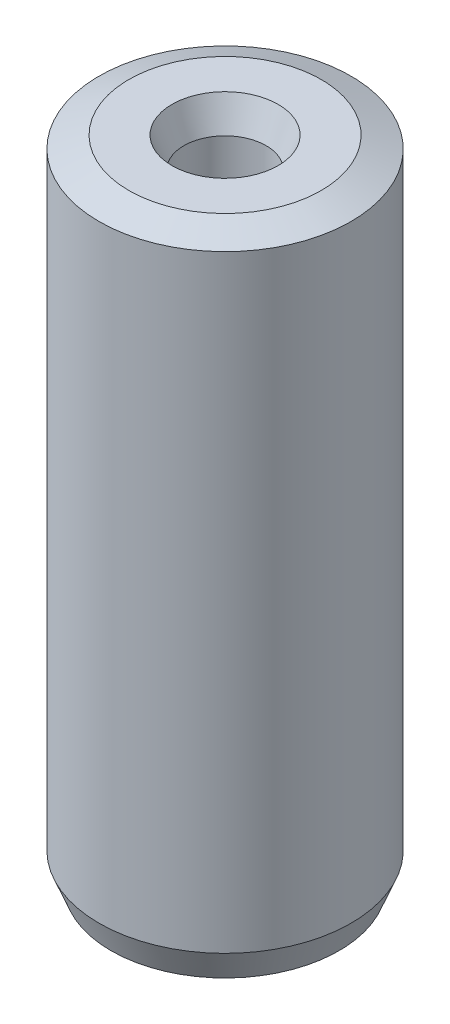
SolidWorks part; units mm, degrees
ref_plane "Front Plane" through (0, 0, 0) normal (0, 0, 1) x (1, 0, 0)
ref_plane "Top Plane" through (0, 0, 0) normal (0, 1, 0) x (1, 0, 0)
ref_plane "Right Plane" through (0, 0, 0) normal (1, 0, 0) x (0, 0, -1)
sketch "Sketch1" plane through (0, 0, 0) normal (0, 1, 0) x (1, 0, 0)
  circle A0 centre (0, 0) radius 5
  dimension "SLEEVE_OD" = 10
extrude "Boss-Extrude1" add sketch "Sketch1" along normal blind 25.7761
sketch "Sketch2" plane through (0, 0, 0) normal (0, 1, 0) x (1, 0, 0)
  circle A0 centre (0, 0) radius 1.6328
  dimension "BORE_D" = 3.2655
extrude "Cut-Extrude1" cut sketch "Sketch2" along normal through all
chamfer "Chamfer1" distance 0.4742 angle 68.144 4 edges at (0, 25.7761, 1.6328) (0, 0, 1.6328) (0, 0, 5) (0, 25.7761, 5) first distance on face at (0, 25.7761, 1.6328) first distance on face at (0, 0, 1.6328) first distance on face at (0, 25.7761, 5)
